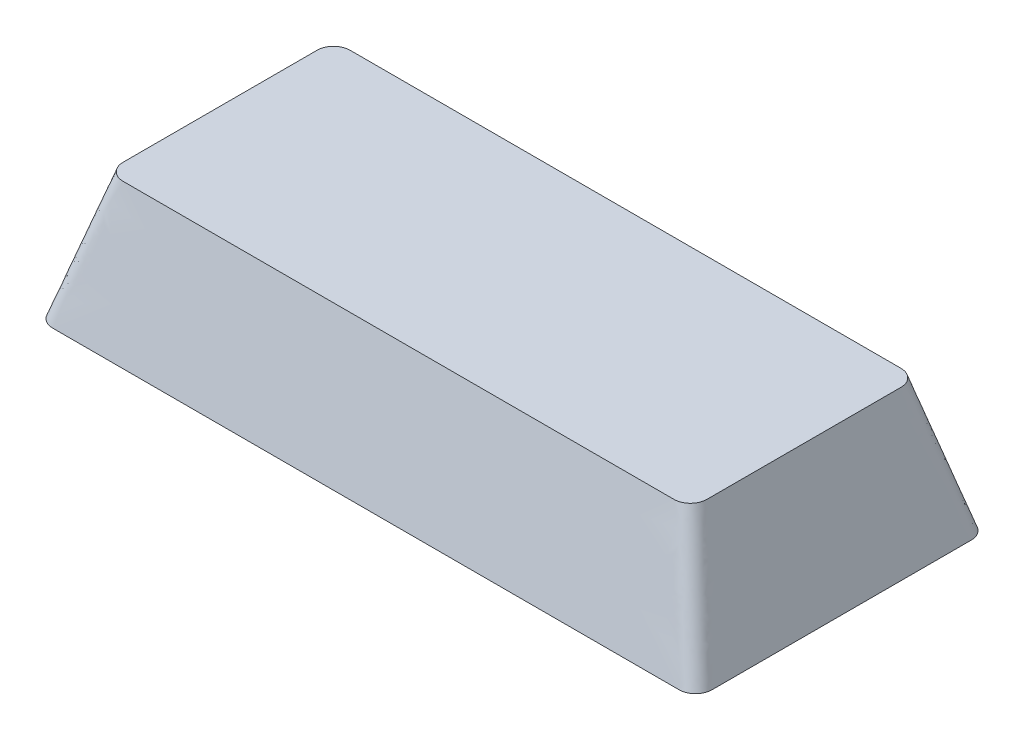
SolidWorks part; units mm, degrees
ref_plane "Alzado" through (0, 0, 0) normal (0, 0, 1) x (1, 0, 0)
ref_plane "Planta" through (0, 0, 0) normal (0, 1, 0) x (1, 0, 0)
ref_plane "Vista lateral" through (0, 0, 0) normal (1, 0, 0) x (0, 0, -1)
sketch "Croquis2" plane through (0, 0, 0) normal (0, 1, 0) x (1, 0, 0)
  line L1 (-19.304, -9.0043) -> (19.304, -9.0043)
  line L2 (-20.32, -7.9883) -> (-20.32, 7.9883)
  line L3 (-19.304, 9.0043) -> (19.304, 9.0043)
  line L4 (20.32, -7.9883) -> (20.32, 7.9883)
  arc A0 (-20.32, 7.9883) -> (-19.304, 9.0043) centre (-19.304, 7.9883) cw
  arc A1 (-19.304, -9.0043) -> (-20.32, -7.9883) centre (-19.304, -7.9883) cw
  arc A2 (19.304, -9.0043) -> (20.32, -7.9883) centre (19.304, -7.9883) ccw
  arc A3 (19.304, 9.0043) -> (20.32, 7.9883) centre (19.304, 7.9883) cw
  point P4 (20.32, 0)
  point P6 (0, 9.0043)
  dimension "D3" = 1.016
  dimension "D1" = 40.64
  dimension "D2" = 18.0086
ref_plane "Plano1" through (0, 8.001, 0) normal (0, 1, 0) x (1, 0, 0)
sketch "Croquis3" plane through (0, 8.001, 0) normal (0, 1, 0) x (1, 0, 0)
  line L1 (-16.9799, -6.9977) -> (16.9799, -6.9977)
  line L2 (-17.9959, -5.9817) -> (-17.9959, 5.9817)
  line L3 (-16.9799, 6.9977) -> (16.9799, 6.9977)
  line L4 (17.9959, -5.9817) -> (17.9959, 5.9817)
  line L5 (-17.9959, -6.9977) -> (17.9959, 6.9977) construction
  line L6 (-17.9959, 6.9977) -> (17.9959, -6.9977) construction
  arc A0 (16.9799, 6.9977) -> (17.9959, 5.9817) centre (16.9799, 5.9817) cw
  arc A1 (16.9799, -6.9977) -> (17.9959, -5.9817) centre (16.9799, -5.9817) ccw
  arc A2 (-16.9799, -6.9977) -> (-17.9959, -5.9817) centre (-16.9799, -5.9817) cw
  arc A3 (-17.9959, 5.9817) -> (-16.9799, 6.9977) centre (-16.9799, 5.9817) cw
  point P0 (0, 0)
  dimension "D3" = 1.016
  dimension "D1" = 35.9918
  dimension "D2" = 13.9954
loft "Recubrir1" add profiles "Croquis3", "Croquis2"
